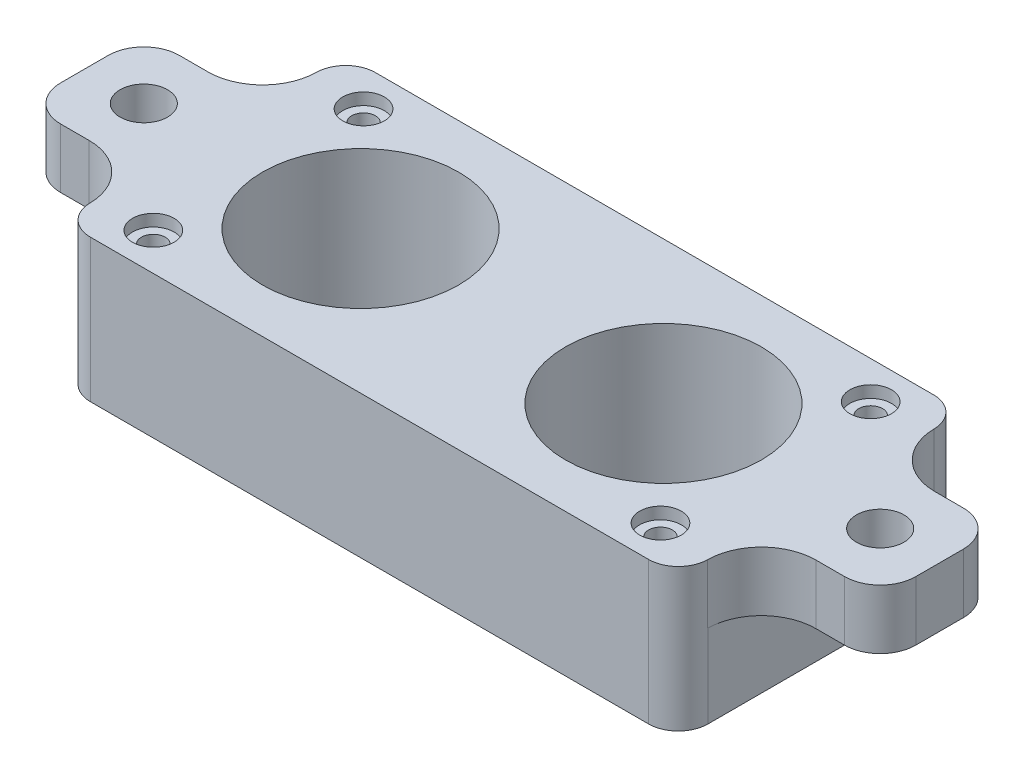
SolidWorks part; units mm, degrees
ref_plane "Front Plane" through (0, 0, 0) normal (0, 0, 1) x (1, 0, 0)
ref_plane "Top Plane" through (0, 0, 0) normal (0, 1, 0) x (1, 0, 0)
ref_plane "Right Plane" through (0, 0, 0) normal (1, 0, 0) x (0, 0, -1)
sketch "Sketch1" plane through (0, 0, 0) normal (0, 1, 0) x (1, 0, 0)
  line L0 (-12.75, 0) -> (12.75, 0) construction
  line L1 (-26, 12) -> (26, 12)
  line L2 (-26, 12) -> (-26, -12)
  line L3 (-26, -12) -> (26, -12)
  line L4 (26, 12) -> (26, -12)
  line L5 (-26, 12) -> (26, -12) construction
  line L6 (-26, -12) -> (26, 12) construction
  circle A0 centre (12.75, 0) radius 8.25
  circle A1 centre (-12.75, 0) radius 8.25
  point P0 (0, 0)
  point P9 (0, 0)
  dimension "D3" = 16.5
  dimension "D1" = 52
  dimension "D2" = 24
  dimension "D4" = 25.5
extrude "Boss-Extrude1" add sketch "Sketch1" along normal blind 12
sketch "Sketch2" plane through (0, 12, 0) normal (0, 1, 0) x (1, 0, 0)
  line L1 (-21.35, 8.85) -> (21.35, 8.85) construction
  line L2 (-21.35, 8.85) -> (-21.35, -8.85) construction
  line L3 (-21.35, -8.85) -> (21.35, -8.85) construction
  line L4 (21.35, 8.85) -> (21.35, -8.85) construction
  line L5 (-21.35, 8.85) -> (21.35, -8.85) construction
  line L6 (-21.35, -8.85) -> (21.35, 8.85) construction
  circle A0 centre (-21.35, 8.85) radius 1
  circle A1 centre (21.35, 8.85) radius 1
  circle A2 centre (21.35, -8.85) radius 1
  circle A3 centre (-21.35, -8.85) radius 1
  point P0 (0, 0)
  dimension "D3" = 2
  dimension "D1" = 17.7
  dimension "D2" = 42.7
extrude "Cut-Extrude1" cut sketch "Sketch2" against normal through all
sketch "Sketch3" plane through (0, 12, 0) normal (0, 1, 0) x (1, 0, 0)
  circle A20 centre (-21.35, 8.85) radius 1.75
  circle A21 centre (21.35, 8.85) radius 1.75
  circle A23 centre (21.35, -8.85) radius 1.75
  circle A24 centre (-21.35, -8.85) radius 1.75
  dimension "D1" = 3.5
extrude "Cut-Extrude2" cut sketch "Sketch3" against normal blind 1
fillet "Fillet1" radius 2.5 4 edges at (26, 6, 12) (-26, 6, 12) (26, 6, -12) (-26, 6, -12)
sketch "Sketch4" plane through (0, 0, 0) normal (0, -1, 0) x (1, 0, 0)
  line L0 (23.5, -12) -> (-23.5, -12) construction
  line L1 (-6, -12) -> (6, -12)
  line L2 (-6, -12) -> (-6, -5)
  line L3 (-6, -5) -> (6, -5)
  line L4 (6, -12) -> (6, -5)
  line L5 (0, -5) -> (0, 0)
  line M14 (-23.5, -12) -> (23.5, -12)
  dimension "D1" = 7
  dimension "D2" = 12
extrude "Cut-Extrude3" cut sketch "Sketch4" against normal blind 5 contours L4 L3 L2 M14 region at (0, 0, -8.5)
fillet "Fillet2" radius 0.5 8 edges at (6, 2.5, -12) (0, 5, -12) (-6, 2.5, -12) (-6, 5, -8.5) (6, 5, -8.5) (6, 2.5, -5) (0, 5, -5) (-6, 2.5, -5)
sketch "Sketch6" plane through (0, 12, 0) normal (0, 1, 0) x (1, 0, 0)
  line L0 (-26, 9.5) -> (-26, -9.5) construction
  line L1 (-26, 5) -> (-36, 5)
  line L2 (-26, 5) -> (-26, -5)
  line L3 (-26, -5) -> (-36, -5)
  line L4 (-36, 5) -> (-36, -5)
  line L5 (0, 0) -> (-36, 0) construction
  line L6 (0, 0) -> (0, 20.5349) construction
  line L7 (36, 5) -> (36, -5)
  line L8 (26, -5) -> (36, -5)
  line L9 (26, 5) -> (26, -5)
  line L10 (26, 5) -> (36, 5)
  circle A0 centre (-31, 0) radius 2
  circle A1 centre (31, 0) radius 2
  dimension "D1" = 4
  dimension "D4" = 5
  dimension "D2" = 10
  dimension "D3" = 10
extrude "Boss-Extrude2" add sketch "Sketch6" against normal blind 5
fillet "Fillet3" radius 4.6 4 edges at (26, 9.5, 5) (-26, 9.5, -5) (-26, 9.5, 5) (26, 9.5, -5)
fillet "Fillet4" radius 3 4 edges at (36, 9.5, -5) (36, 9.5, 5) (-36, 9.5, 5) (-36, 9.5, -5)
